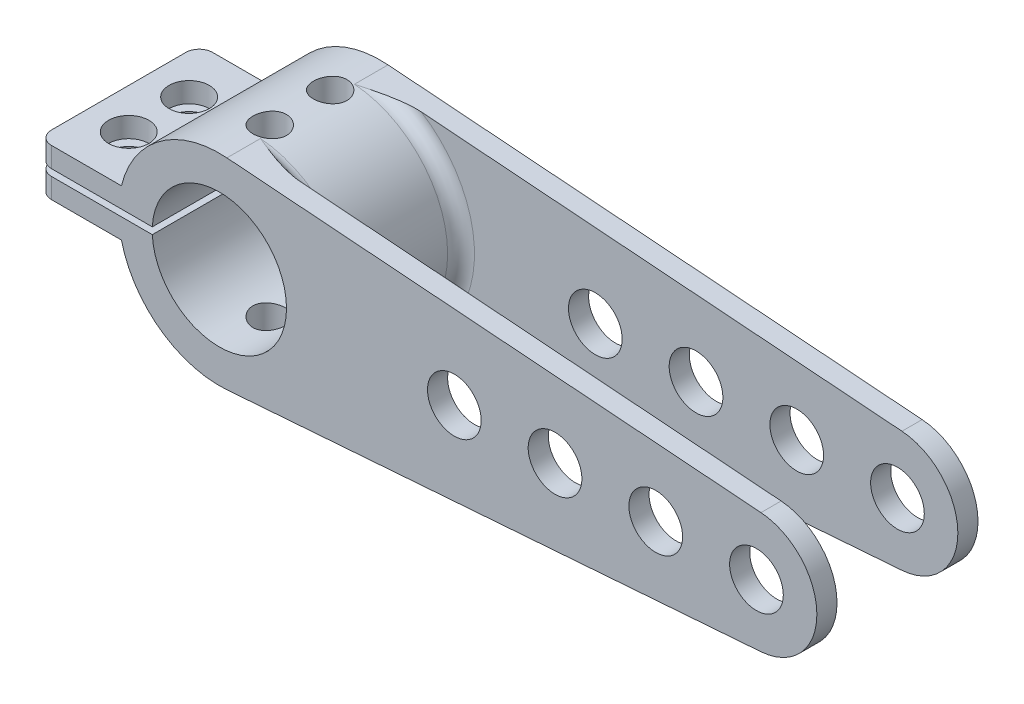
SolidWorks part; units mm, degrees
ref_plane "前视基准面" through (0, 0, 0) normal (0, 0, 1) x (1, 0, 0)
ref_plane "上视基准面" through (0, 0, 0) normal (0, 1, 0) x (1, 0, 0)
ref_plane "右视基准面" through (0, 0, 0) normal (1, 0, 0) x (0, 0, -1)
sketch "草图1" plane through (0, 0, 0) normal (0, 0, 1) x (1, 0, 0)
  line L0 (1.125, 14.9578) -> (80.675, 8.9747)
  line L1 (1.125, -14.9578) -> (80.675, -8.9747)
  circle A0 centre (0, 0) radius 10
  circle A1 centre (80, 0) radius 4
  circle A2 centre (65, 0) radius 4
  circle A3 centre (50, 0) radius 4
  circle A4 centre (35, 0) radius 4
  circle A5 centre (0, 0) radius 15
  circle A6 centre (80, 0) radius 9
  point P3 (80, 0)
  point P6 (65, 0)
  point P7 (50, 0)
  point P8 (35, 0)
  dimension "D1" = 20
  dimension "D3" = 8
  dimension "D7" = 8
  dimension "D8" = 8
  dimension "D9" = 8
  dimension "D10" = 30
  dimension "D11" = 18
  dimension "D2" = 80
  dimension "D4" = 15
  dimension "D5" = 15
  dimension "D6" = 15
extrude "凸台-拉伸1" add sketch "草图1" along normal blind 24 contours A6 L0 A5 L1 A2 A3 A4 | A5 A0 | A6 A1 region at (39.505, 0, 0) region at (10.6861, 9.9126, 0) region at (86.4117, 5.9475, 0)
ref_plane "基准面4" through (0, 0, 3) normal (0, 0, 1) x (1, 0, 0)
sketch "草图3" plane through (0, 0, 3) normal (0, 0, 1) x (1, 0, 0)
  line L0 (1.125, 14.9578) -> (80.675, 8.9747)
  line L1 (1.125, -14.9578) -> (80.675, -8.9747)
  circle A0 centre (0, 0) radius 15
  circle A1 centre (80, 0) radius 9
  point P3 (80, 0)
  dimension "D1" = 30
  dimension "D2" = 18
  dimension "D3" = 80
extrude "切除-拉伸1" cut sketch "草图3" along normal blind 18 contours A1 L0 A0 L1 | A1 region at (40.6004, 0, 3) region at (80, 0, 3)
fillet "圆角1" radius 2 2 edges at (15, 0, 21) (15, 0, 3)
sketch "草图4" plane through (0, 0, 0) normal (0, 1, 0) x (1, 0, 0)
  circle A0 centre (0, -7.5) radius 2.5
  circle A1 centre (0, -16.5) radius 2.5
  point P0 (0, -7.5)
  point P1 (0, -16.5)
  dimension "D3" = 5
  dimension "D4" = 5
  dimension "D1" = 7.5
  dimension "D2" = 16.5
extrude "切除-拉伸2" cut sketch "草图4" against normal through all both and the other way through all
sketch "草图5" plane through (0, 0, 0) normal (0, 1, 0) x (1, 0, 0)
  line L0 (1.125, 0) -> (-15, 0) construction
  line L1 (-10, 0) -> (-27, 0)
  line L2 (-10, 0) -> (-10, -24)
  line L3 (-10, -24) -> (-27, -24)
  line L4 (-27, 0) -> (-27, -24)
  circle A0 centre (-21, -7.5) radius 3
  circle A1 centre (-21, -16.5) radius 3
  dimension "D4" = 6
  dimension "D8" = 6
  dimension "D9" = 6
  dimension "D1" = 24
  dimension "D2" = 10
  dimension "D3" = 17
  dimension "D5" = 6
  dimension "D6" = 7.5
  dimension "D7" = 7.5
extrude "凸台-拉伸2" add sketch "草图5" along normal mid plane 7
sketch "草图7" plane through (0, 0, 0) normal (0, 1, 0) x (1, 0, 0)
  line L0 (-14.586, -24) -> (1.125, -24) construction
  line L1 (-27, 0) -> (0, 0)
  line L2 (-27, 0) -> (-27, -24)
  line L3 (-27, -24) -> (0, -24)
  line L4 (0, 0) -> (0, -24)
  dimension "D1" = 27
extrude "切除-拉伸3" cut sketch "草图7" against normal mid plane 1
fillet "圆角2" radius 2 4 edges at (-27, -2, 0) (-27, 2, 0) (-27, -2, 24) (-27, 2, 24)
